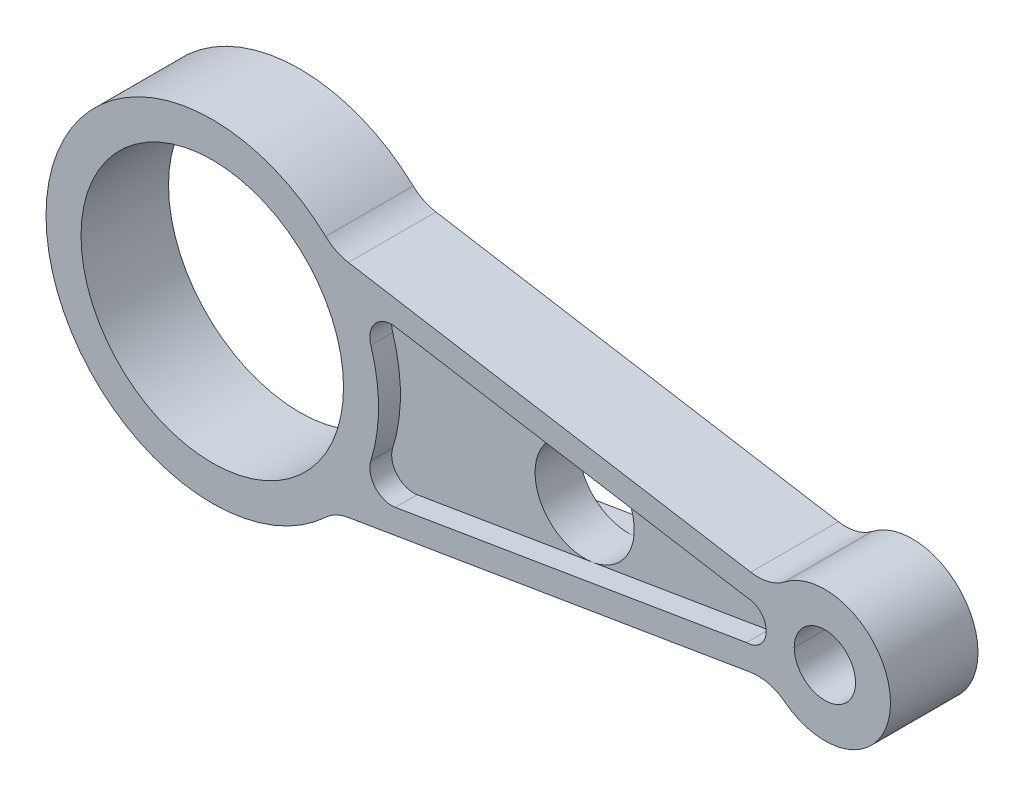
SolidWorks part; units mm, degrees
material "Plain Carbon Steel"
ref_plane "Front Plane" through (0, 0, 0) normal (0, 0, 1) x (1, 0, 0)
ref_plane "Top Plane" through (0, 0, 0) normal (0, 1, 0) x (1, 0, 0)
ref_plane "Right Plane" through (0, 0, 0) normal (1, 0, 0) x (0, 0, -1)
sketch "Sketch1" plane through (0, 0, 0) normal (0, 0, 1) x (1, 0, 0)
  line L0 (0, 0) -> (140, 0) construction
  line L1 (128.0638, 9.0844) -> (27.9355, 25.7606)
  line L2 (27.9355, -25.7606) -> (128.0638, -9.0844)
  circle A0 centre (0, 0) radius 30
  circle A1 centre (140, 0) radius 7
  arc A2 (27.9355, 25.7606) -> (27.9355, -25.7606) centre (0, 0) ccw
  arc A3 (128.0638, -9.0844) -> (128.0638, 9.0844) centre (140, 0) ccw
  arc A4 (38, 0) -> (27.9355, 25.7606) centre (0, 0) ccw construction
  arc A5 (27.9355, -25.7606) -> (38, 0) centre (0, 0) ccw construction
  arc A6 (128.0638, 9.0844) -> (125, 0) centre (140, 0) ccw construction
  arc A7 (125, 0) -> (128.0638, -9.0844) centre (140, 0) ccw construction
  dimension "D1" = 60
  dimension "D2" = 14
  dimension "D3" = 76
  dimension "D4" = 30
  dimension "D5" = 140
extrude "Boss-Extrude1" add sketch "Sketch1" along normal mid plane 20
fillet "Fillet1" radius 10 2 edges at (27.9355, 25.7606, 0) (27.9355, -25.7606, 0)
fillet "Fillet3" radius 10 2 edges at (128.0638, 9.0844, 0) (128.0638, -9.0844, 0)
sketch "Sketch2" plane through (0, 0, 10) normal (0, 0, 1) x (1, 0, 0)
  line L0 (0, 0) -> (140, 0) construction
  line L1 (41.8286, 17.871) -> (122.1113, 4.5)
  line L2 (41.8286, -17.871) -> (122.1113, -4.5)
  line L3 (123.0688, 9.9163) -> (31.1011, 25.2334) construction
  line L4 (31.1011, -25.2334) -> (123.0688, -9.9163) construction
  arc A0 (122.1113, -4.5) -> (122.1113, 4.5) centre (122.1113, 0) ccw
  arc A1 (41.8286, 17.871) -> (36.2389, 11.4344) centre (41.0071, 12.9389) ccw
  arc A2 (36.2389, 11.4344) -> (36.2389, -11.4344) centre (0, 0) cw
  arc A3 (36.2389, -11.4344) -> (41.8286, -17.871) centre (41.0071, -12.9389) ccw
  circle A4 centre (0, 0) radius 30 construction
  dimension "D3" = 4.5
  dimension "D4" = 5
  dimension "D5" = 8
  dimension "D1" = 5.5
  dimension "D2" = 5.5
extrude "Cut-Extrude1" cut sketch "Sketch2" against normal blind 5
mirror "Mirror1" about plane through (0, 0, 0) normal (0, 0, 1) of "Cut-Extrude1"
split line "Split Line1"
sketch "Sketch12" plane through (0, 0, 0) normal (0, 0, 1) x (1, 0, 0)
  line L0 (0, 0) -> (140, 0) construction
  line L1 (41.8286, 17.871) -> (122.1113, 4.5)
  line L2 (41.8286, -17.871) -> (122.1113, -4.5)
  line L3 (123.0688, 9.9163) -> (31.1011, 25.2334) construction
  line L4 (31.1011, -25.2334) -> (123.0688, -9.9163) construction
  arc A0 (122.1113, -4.5) -> (122.1113, 4.5) centre (122.1113, 0) ccw
  arc A1 (41.8286, 17.871) -> (36.2389, 11.4344) centre (41.0071, 12.9389) ccw
  arc A2 (36.2389, 11.4344) -> (36.2389, -11.4344) centre (0, 0) cw
  arc A3 (36.2389, -11.4344) -> (41.8286, -17.871) centre (41.0071, -12.9389) ccw
  circle A4 centre (80.107, 0) radius 11.3396
  circle A5 centre (0, 0) radius 30 construction
  point P16 (81.9699, 11.1855)
  dimension "D3" = 4.5
  dimension "D4" = 5
  dimension "D1" = 8
  dimension "D2" = 5.5
extrude "Cut-Extrude3" cut sketch "Sketch12" against normal through all from surface contours A4 starting at face at (140, 0, 10)
